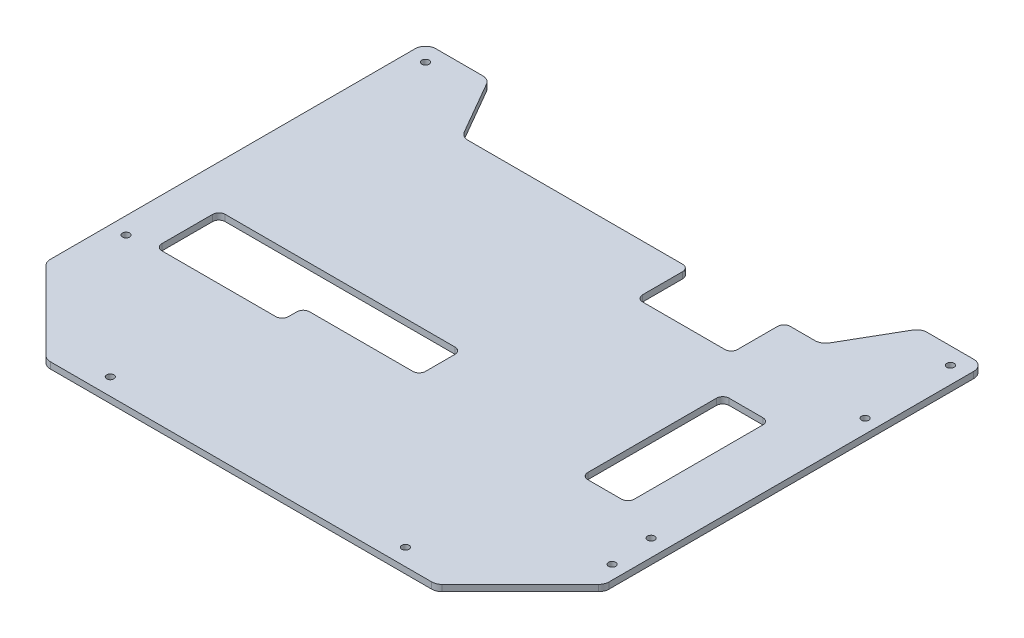
SolidWorks part; units mm, degrees
material "Acier non allié"
ref_plane "Front" through (0, 0, 0) normal (0, 0, 1) x (1, 0, 0)
ref_plane "Top" through (0, 0, 0) normal (0, 1, 0) x (1, 0, 0)
ref_plane "Right" through (0, 0, 0) normal (1, 0, 0) x (0, 0, -1)
sketch "Esquisse1" plane through (0, 0, 0) normal (0, 1, 0) x (1, 0, 0)
  line L0 (0, 0) -> (0, 1919.0564) construction
  line L1 (-92.5, 0) -> (92.5, 0)
  line L2 (92.5, 0) -> (132.5, 40)
  line L3 (132.5, 40) -> (132.5, 220)
  line L4 (132.5, 220) -> (102.5, 220)
  line L5 (102.5, 220) -> (85.1795, 190)
  line L6 (85.1795, 190) -> (-85.1795, 190)
  line L7 (-102.5, 220) -> (-85.1795, 190)
  line L8 (-132.5, 220) -> (-102.5, 220)
  line L9 (-132.5, 40) -> (-132.5, 220)
  line L10 (-92.5, 0) -> (-132.5, 40)
  point P12 (0, 190)
  dimension "D1" = 132.5
  dimension "D2" = 220
  dimension "D3" = 30
  dimension "D4" = 30
  dimension "D5" = 40
  dimension "D6" = 40
  dimension "D7" = 60
extrude "Boss.-Extru.1" add sketch "Esquisse1" along normal blind 3
fillet "Congé1" radius 5 10 edges at (132.5, 1.5, -220) (102.5, 1.5, -220) (85.1795, 1.5, -190) (-85.1795, 1.5, -190) (-102.5, 1.5, -220) (-132.5, 1.5, -220) (-132.5, 1.5, -40) (-92.5, 1.5, 0) (92.5, 1.5, 0) (132.5, 1.5, -40)
sketch "Esquisse2" plane through (0, 0, 0) normal (0, -1, 0) x (1, 0, 0)
  line L0 (0, 0) -> (0, -330.9968) construction
  line L1 (-90.4289, 0) -> (90.4289, 0) construction
  line L2 (-105.3868, -220) -> (-127.5, -220) construction
  line L3 (-132.5, -215) -> (-132.5, -42.0711) construction
  line L4 (-90.4289, 0) -> (90.4289, 0) construction
  line L5 (132.5, -42.0711) -> (132.5, -215) construction
  line L6 (127.5, -220) -> (105.3868, -220) construction
  circle A0 centre (-70, -8) radius 1
  circle A1 centre (-124.5, -70) radius 1
  circle A2 centre (-124.5, -212) radius 1
  circle A3 centre (124.5, -212) radius 1
  circle A4 centre (124.5, -70) radius 1
  circle A5 centre (70, -8) radius 1
  circle A6 centre (126, -50) radius 1.5
  circle A7 centre (126, -170) radius 1.5
  dimension "D3" = 2
  dimension "D6" = 2
  dimension "D9" = 2
  dimension "D12" = 3
  dimension "D15" = 3
  dimension "D1" = 70
  dimension "D2" = 8
  dimension "D4" = 124.5
  dimension "D5" = 70
  dimension "D7" = 8
  dimension "D8" = 8
  dimension "D10" = 50
  dimension "D11" = 6.5
  dimension "D13" = 50
  dimension "D14" = 6.5
extrude "Enlèv. mat.-Extru.1" cut sketch "Esquisse2" against normal through all
hole_wizard "Dégagement M31" positions "Esquisse3" profile "Esquisse4" hole size "M3" standard "ISO" end condition through all
sketch "Esquisse3" plane through (0, 0, 0) normal (0, -1, 0) x (-1, 0, 0)
  point P0 (-70, 8)
  point P3 (-124.5, 70)
  point P6 (-124.5, 212)
  point P9 (124.5, 212)
  point P12 (124.5, 70)
  point P15 (70, 8)
  point P18 (-126, 170)
  point P21 (-126, 50)
sketch "Esquisse4" plane through (70, 0, -8) normal (1, 0, 0) x (0, 0, -1)
  line L0 (0, 0) -> (0, 3)
  line L1 (0, 3) -> (1.7, 3)
  line L2 (1.7, 3) -> (1.7, 0)
  line L5 (1.7, 0) -> (0, 0)
  line L11 (0, -6.35) -> (0, 107.95) construction
  dimension "Diamètre du perçage jusqu'au prochain" = 3.4
  dimension "Profondeur du perçage jusqu'au prochain" = 3
sketch "Esquisse5" plane through (0, 0, 0) normal (0, -1, 0) x (1, 0, 0)
  line L6 (82.2927, -190) -> (-82.2927, -190) construction
  line L7 (22.5, -190) -> (67.5, -190)
  line L20 (22.5, -190) -> (22.5, -165)
  line L21 (22.5, -165) -> (67.5, -165)
  line L22 (67.5, -190) -> (67.5, -165)
  line L23 (132.5, -42.0711) -> (132.5, -215) construction
  line L24 (-112.5, -82) -> (-112.5, -72)
  line L25 (-112.5, -102) -> (2.5, -102)
  line L26 (-112.5, -102) -> (-112.5, -82)
  line L27 (-52.5, -82) -> (2.5, -82)
  line L28 (2.5, -102) -> (2.5, -82)
  line L29 (-132.5, -215) -> (-132.5, -42.0711) construction
  line L30 (127.5, -220) -> (105.3868, -220) construction
  line L31 (82.5, -146) -> (104.5, -146)
  line L32 (82.5, -146) -> (82.5, -79)
  line L33 (82.5, -79) -> (104.5, -79)
  line L34 (104.5, -146) -> (104.5, -79)
  line L35 (-90.4289, 0) -> (90.4289, 0) construction
  line L36 (-112.5, -72) -> (-52.5, -72)
  line L37 (-52.5, -82) -> (-52.5, -72)
  dimension "D1" = 65
  dimension "D2" = 110
  dimension "D3" = 25
  dimension "D4" = 82
  dimension "D5" = 135
  dimension "D6" = 20
  dimension "D7" = 115
  dimension "D8" = 50
  dimension "D9" = 74
  dimension "D10" = 67
  dimension "D11" = 22
  dimension "D15" = 30
  dimension "D16" = 60
extrude "Enlèv. mat.-Extru.2" cut sketch "Esquisse5" against normal through all
fillet "Congé2" radius 3 14 edges at (67.5, 1.5, -190) (67.5, 1.5, -165) (22.5, 1.5, -165) (22.5, 1.5, -190) (104.5, 1.5, -146) (82.5, 1.5, -146) (82.5, 1.5, -79) (104.5, 1.5, -79) (2.5, 1.5, -82) (2.5, 1.5, -102) (-112.5, 1.5, -102) (-52.5, 1.5, -72) (-52.5, 1.5, -82) (-112.5, 1.5, -72)
equation "\"WIDTH\"= 300mm'Total width of the robot"
equation "\"LENGTH\"= 220mm'Total length of the robot"
equation "\"CUT_DEPTH\"= 45mm'Depth of the cut on the edges of the plate"
equation "\"Plate_th\"= 3mm'Thickness of the plate"
equation "\"D1\"= \"Plate_th\""
